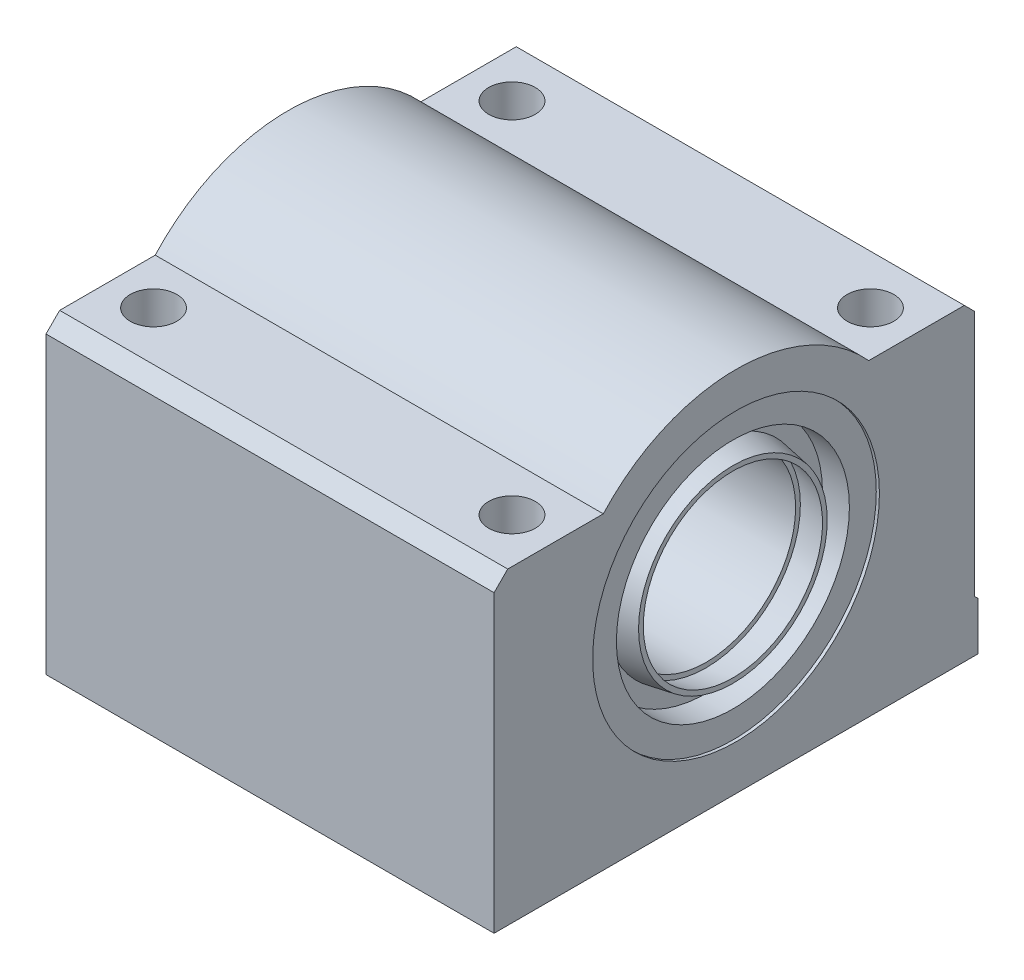
SolidWorks part; units mm, degrees
ref_plane "Front Plane" through (0, 0, 0) normal (0, 0, 1) x (1, 0, 0)
ref_plane "Top Plane" through (0, 0, 0) normal (0, 1, 0) x (1, 0, 0)
ref_plane "Right Plane" through (0, 0, 0) normal (1, 0, 0) x (0, 0, -1)
sketch "Layout Sketch 1" plane through (0, 0, 0) normal (0, 1, 0) x (1, 0, 0)
  line L0 (25, 0) -> (-25, 0) construction
  line L1 (0, -27) -> (0, 27) construction
  line L3 (-20, -20) -> (20, -20) construction
  line L4 (-20, -20) -> (-20, 20) construction
  line L5 (-20, 20) -> (20, 20) construction
  line L6 (20, -20) -> (20, 20) construction
  line L7 (-20, -20) -> (20, 20) construction
  line L8 (-20, 20) -> (20, -20) construction
  circle A2 centre (-20, -20) radius 2.6 construction
  circle A3 centre (20, 20) radius 2.6 construction
  circle A4 centre (-20, -20) radius 2.6 construction
  circle A5 centre (20, 20) radius 2.6 construction
  point P0 (0, 0)
  point P4 (0, 0)
  point P8 (0, 0)
  point P14 (-20, 20)
  point P15 (20, 20)
  point P16 (20, -20)
  point P17 (-20, -20)
  dimension "MountingHoleDiameter" = 5.2
  dimension "ThruHoleDIA" = 5.2
  dimension "OALength" = 50
  dimension "OAWidth" = 54
  dimension "HoleCenterWidth" = 40
  dimension "HoleCenterLength" = 40
sketch "Layout Sketch 2" plane through (0, 0, 0) normal (1, 0, 0) x (0, 0, -1)
  line L0 (-20, 0) -> (20, 0) construction
  line L1 (0, 0) -> (0, 41) construction
  line L2 (-27, 0) -> (27, 0) construction
  line L3 (-27, 0) -> (27, 0) construction
  line L4 (27, 34.44) -> (-27, 34.44) construction
  line L5 (-27, 0) -> (-27, 34.44) construction
  circle A0 centre (0, 21) radius 10
  circle A1 centre (0, 21) radius 20 construction
  point P9 (-27, 17.22)
  point P12 (0, 34.44)
  point P15 (0, 34.44)
  point P19 (0, 41)
  point P20 (-14.811, 34.44)
  dimension "ShaftDiameter" = 20
  dimension "CenterHeight" = 21
  dimension "OAHeight" = 41
  dimension "D1" = 34.44
  dimension "D2" = 12.189
sketch "Sketch3" plane through (0, 0, 0) normal (1, 0, 0) x (0, 0, -1)
  line L0 (27, 0) -> (27, 34.44)
  line L6 (-27, 34.44) -> (-27, 0)
  line L7 (-27, 0) -> (27, 0)
  line L8 (-27, 34.44) -> (-14.811, 34.44)
  line L9 (14.811, 34.44) -> (27, 34.44)
  circle A0 centre (0, 21) radius 10 construction
  circle A1 centre (0, 21) radius 10
  arc A2 (-14.811, 34.44) -> (14.811, 34.44) centre (0, 21) cw
  circle A3 centre (0, 21) radius 20 construction
extrude "Boss-Extrude1" add sketch "Sketch3" along normal up to vertex (25 mm away) and the other way up to vertex (25 mm away) up to point (25, 0, 0) other way up to point (-25, 0, 0)
sketch "Sketch4" plane through (25, 0, 0) normal (1, 0, 0) x (0, 0, -1)
  line L0 (0, 37) -> (0, 41) construction
  circle A0 centre (0, 21) radius 16
  arc A1 (14.811, 34.44) -> (-14.811, 34.44) centre (0, 21) ccw construction
  dimension "D1" = 4
extrude "Cut-Extrude1" cut sketch "Sketch4" against normal blind 3.35
sketch "Sketch5" plane through (21.65, 0, 0) normal (1, 0, 0) x (0, 0, -1)
  line L0 (0, 34) -> (0, 37) construction
  circle A0 centre (0, 21) radius 16 construction
  circle A1 centre (0, 21) radius 16
  circle A2 centre (0, 21) radius 13
  dimension "D1" = 3
extrude "Boss-Extrude2" add sketch "Sketch5" along normal blind 3
sketch "Sketch6" plane through (0, 0, 0) normal (0, 0, 1) x (1, 0, 0)
  line L0 (24.65, 8) -> (24.65, 34) construction
  line L1 (21.65, 8) -> (21.65, 34) construction
  line L2 (24.65, 8) -> (24.65, 34) construction
  line L3 (21.65, 8) -> (21.65, 34) construction
  line L4 (-24.65, 21) -> (24.65, 21) construction
  line L5 (24.65, 31) -> (24.65, 31.529)
  line L6 (24.65, 31.529) -> (21.65, 32.058)
  line L7 (21.65, 32.058) -> (21.65, 31.529)
  line L8 (21.65, 31.529) -> (24.65, 31)
  line L9 (21.65, 11) -> (21.65, 31) construction
  line L10 (21.65, 11) -> (21.65, 31) construction
  line L11 (21.65, 31.529) -> (21.65, 31) construction
  point P7 (0, 21)
  dimension "D1" = 10
revolve "Revolve1" add sketch "Sketch6" angle 360 about L4
mirror "Mirror1" about plane through (0, 0, 0) normal (1, 0, 0) of "Revolve1", "Boss-Extrude2", "Cut-Extrude1"
chamfer "Chamfer1" distance 1.5236 angle 45 2 edges at (0, 34.44, -27) (0, 34.44, 27)
sketch "Sketch7" plane through (25, 0, 0) normal (1, 0, 0) x (0, 0, -1)
  line L0 (26.6191, 0) -> (26.6191, 5.75) construction
  line L1 (-27, 0) -> (27, 0) construction
  line L2 (26.6191, 5.75) -> (27, 5.3691)
  line L3 (27, 0) -> (27, 32.9164) construction
  line L4 (26.6191, 5.75) -> (26.6191, 33.2973)
  line L6 (26.6191, 33.2973) -> (27, 32.9164)
  line L7 (27, 32.9164) -> (27, 5.3691)
  line L8 (27, 32.9164) -> (25.4764, 34.44) construction
  dimension "D1" = 45
  dimension "D2" = 0.3809
  dimension "D3" = 5.75
extrude "Cut-Extrude2" cut sketch "Sketch7" against normal through all
sketch "Sketch11" plane through (0, 0, 0) normal (0, -1, 0) x (1, 0, 0)
  circle A0 centre (-20, 20) radius 2.6
  circle A1 centre (20, 20) radius 2.6
  circle A2 centre (20, -20) radius 2.6
  circle A3 centre (-20, -20) radius 2.6
  circle A4 centre (-20, 20) radius 2.6 construction
extrude "Cut-Extrude6" cut sketch "Sketch11" against normal up to vertex (17.22 mm away) up to point (0, 17.22, 27)
sketch "Sketch12" plane through (0, 0, 0) normal (0, -1, 0) x (1, 0, 0)
  circle A0 centre (-20, 20) radius 2.6
  circle A1 centre (20, 20) radius 2.6
  circle A2 centre (20, -20) radius 2.6
  circle A3 centre (-20, -20) radius 2.6
  circle A4 centre (-20, 20) radius 2.6 construction
extrude "Cut-Extrude7" cut sketch "Sketch12" against normal through all
sketch "SketchX" plane through (0, 0, 0) normal (0, 0, 1) x (1, 0, 0)
  line L0 (17.4, 0) -> (22.6, 0) construction
  line L1 (-22.6, 0) -> (-17.4, 0) construction
  line L2 (17.4, 0) -> (22.6, 0)
  line L3 (-22.6, 0) -> (-17.4, 0)
  line L4 (-17.4, 34.44) -> (-22.6, 34.44) construction
  line L5 (22.6, 34.44) -> (17.4, 34.44) construction
  line L6 (-17.4, 34.44) -> (-22.6, 34.44)
  line L7 (22.6, 34.44) -> (17.4, 34.44)
  line L8 (-22.6, 0) -> (-22.6, 17.22)
  line L9 (-22.6, 34.44) -> (-22.6, 17.22)
  line L11 (-17.4, 34.44) -> (-17.4, 17.22)
  line L13 (-17.4, 17.22) -> (-17.4, 0)
  line L14 (17.4, 0) -> (17.4, 17.22)
  line L16 (17.4, 34.44) -> (17.4, 17.22)
  line L17 (22.6, 34.44) -> (22.6, 17.22)
  line L19 (22.6, 17.22) -> (22.6, 0)
ref_axis "Center Axis 1" through (21.65, 21, 0) along (-1, 0, 0)
ref_plane "Contact Plane 1" through (0, 0, 0) normal (0, -1, 0) x (1, 0, 0)
ref_plane "Contact Plane 2" through (0, 34.44, 0) normal (0, 1, 0) x (1, 0, 0)
equation "\"D1@Layout Sketch 2\"=\"OAHeight@Layout Sketch 2\" * 0.84"
equation "\"D1@Boss-Extrude2\"=\"D1@Cut-Extrude1\"-.35"
equation "\"D2@Sketch7\"=\"D1@Chamfer1\"/4"
equation "\"D1@Chamfer1\"=\"D2@Layout Sketch 2\"/8"
